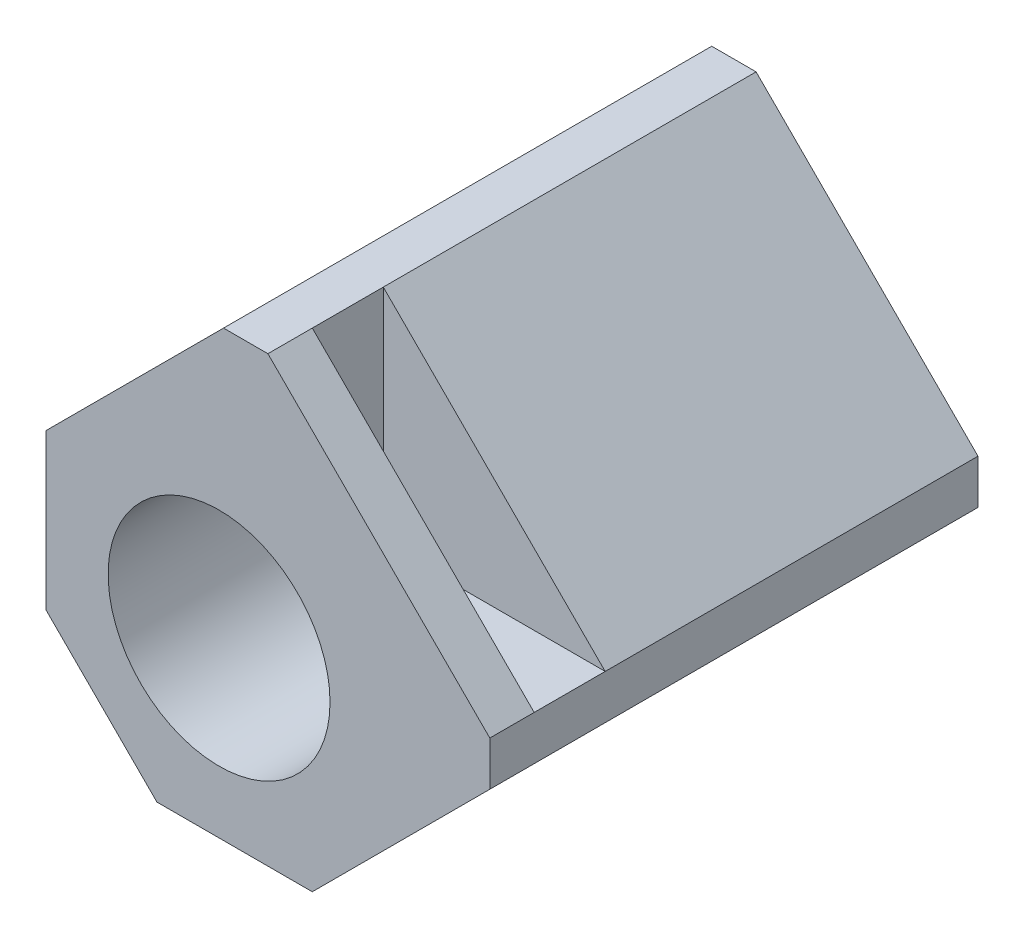
SolidWorks part; units mm, degrees
ref_plane "Plan de face" through (0, 0, 0) normal (0, 0, 1) x (1, 0, 0)
ref_plane "Plan de dessus" through (0, 0, 0) normal (0, 1, 0) x (1, 0, 0)
ref_plane "Plan de droite" through (0, 0, 0) normal (1, 0, 0) x (0, 0, -1)
sketch "Esquisse1" plane through (0, 0, 0) normal (0, 0, 1) x (1, 0, 0)
  line L1 (0, 0) -> (20, 0)
  line L2 (0, 0) -> (0, 20)
  line L3 (0, 20) -> (20, 20)
  line L4 (20, 0) -> (20, 20)
  dimension "D1" = 20
  dimension "D2" = 20
extrude "Boss.-Extru.1" add sketch "Esquisse1" along normal blind 22
chamfer "Chanfrein1" distance 10 angle 45 1 edges at (20, 20, 11)
sketch "Esquisse2" plane through (0, 0, 22) normal (0, 0, 1) x (1, 0, 0)
  line L0 (10, 20) -> (10, 10)
  line L1 (10, 10) -> (20, 10)
  line L2 (20, 10) -> (10, 20)
extrude "Enlèv. mat.-Extru.1" cut sketch "Esquisse2" against normal blind 3.2 from offset 2 offset against normal yes
sketch "Esquisse3" plane through (0, 0, 0) normal (0, 0, -1) x (-1, 0, 0)
  line L0 (-10, 0) -> (-10, 20) construction
  line L1 (0, 0) -> (-20, 0) construction
  line L2 (-20, 10) -> (0, 10) construction
  line L3 (0, 20) -> (0, 0) construction
  circle A0 centre (-7.8, 7.8) radius 2.2
  dimension "D1" = 4.4
extrude "Enlèv. mat.-Extru.2" cut sketch "Esquisse3" against normal through all
sketch "Esquisse4" plane through (0, 0, 22) normal (0, 0, 1) x (1, 0, 0)
  circle A0 centre (7.8, 7.8) radius 5
  dimension "D1" = 10
extrude "Enlèv. mat.-Extru.3" cut sketch "Esquisse4" against normal blind 10.5
chamfer "Chanfrein2" distance 5 angle 45 1 edges at (0, 0, 11)
chamfer "Chanfrein3" distance 8 angle 45 2 edges at (20, 0, 11) (0, 20, 11)
